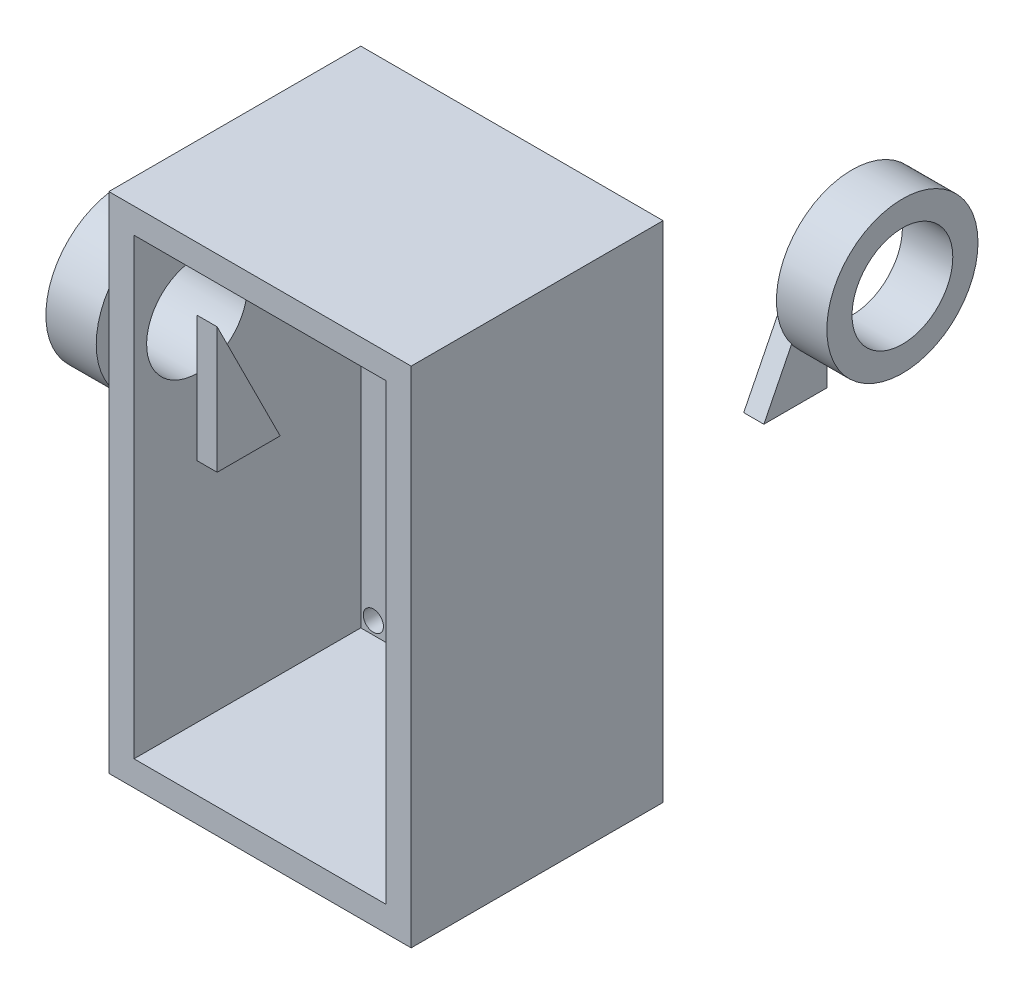
SolidWorks part; units mm, degrees
ref_plane "前视基准面" through (0, 0, 0) normal (0, 0, 1) x (1, 0, 0)
ref_plane "上视基准面" through (0, 0, 0) normal (0, 1, 0) x (1, 0, 0)
ref_plane "右视基准面" through (0, 0, 0) normal (1, 0, 0) x (0, 0, -1)
other "Configuration Table"
sketch "Sketch1" plane through (0, 0, 0) normal (0, 0, 1) x (1, 0, 0)
  line L1 (-60, -100) -> (60, -100)
  line L2 (-60, -100) -> (-60, 100)
  line L3 (-60, 100) -> (60, 100)
  line L4 (60, -100) -> (60, 100)
  line L5 (-60, -100) -> (60, 100) construction
  line L6 (-60, 100) -> (60, -100) construction
  point P0 (0, 0)
extrude "Boss-Extrude1" add sketch "Sketch1" along normal blind 100
ref_plane "Plane1" through (0, 0, 100) normal (0, 0, 1) x (1, 0, 0)
sketch "Sketch2" plane through (0, 0, 100) normal (0, 0, 1) x (1, 0, 0)
  line L1 (-50, -90) -> (50, -90)
  line L2 (-50, -90) -> (-50, 90)
  line L3 (-50, 90) -> (50, 90)
  line L4 (50, -90) -> (50, 90)
  line L5 (-50, -90) -> (50, 90) construction
  line L6 (-50, 90) -> (50, -90) construction
  point P0 (0, 0)
extrude "Cut-Extrude1" cut sketch "Sketch2" against normal blind 90
ref_plane "Plane2" through (-60, 0, 0) normal (1, 0, 0) x (0, 0, -1)
sketch "Sketch3" plane through (-60, 0, 0) normal (1, 0, 0) x (0, 0, -1)
  circle A0 centre (-75, 50) radius 30
extrude "Boss-Extrude2" add sketch "Sketch3" against normal blind 20
ref_plane "Plane3" through (60, 0, 0) normal (1, 0, 0) x (0, 0, -1)
sketch "Sketch4" plane through (60, 0, 0) normal (1, 0, 0) x (0, 0, -1)
  circle A0 centre (75, 50) radius 30
extrude "Boss-Extrude3" add sketch "Sketch4" along normal blind 20
ref_plane "Plane4" through (-80, 0, 0) normal (1, 0, 0) x (0, 0, -1)
sketch "Sketch5" plane through (-80, 0, 0) normal (1, 0, 0) x (0, 0, -1)
  circle A0 centre (-75, 50) radius 20
extrude "Cut-Extrude2" cut sketch "Sketch5" along normal blind 40
ref_plane "Plane5" through (80, 0, 0) normal (1, 0, 0) x (0, 0, -1)
sketch "Sketch6" plane through (80, 0, 0) normal (1, 0, 0) x (0, 0, -1)
  circle A0 centre (75, 50) radius 20
extrude "Cut-Extrude3" cut sketch "Sketch6" against normal blind 40
ref_plane "Plane6" through (-50, 0, 0) normal (1, 0, 0) x (0, 0, -1)
sketch "Sketch7" plane through (-50, 0, 0) normal (1, 0, 0) x (0, 0, -1)
  line L0 (-75, 50) -> (-75, 0)
  line L1 (-75, 0) -> (-50, 0)
  line L2 (-50, 0) -> (-75, 50)
extrude "Boss-Extrude4" add sketch "Sketch7" along normal blind 8
ref_plane "Plane7" through (50, 0, 0) normal (1, 0, 0) x (0, 0, -1)
sketch "Sketch8" plane through (50, 0, 0) normal (1, 0, 0) x (0, 0, -1)
  line L0 (75, 50) -> (75, 0)
  line L1 (75, 0) -> (50, 0)
  line L2 (50, 0) -> (75, 50)
extrude "Boss-Extrude5" add sketch "Sketch8" against normal blind 8
ref_plane "Plane8" through (0, 0, 0) normal (0, 0, 1) x (1, 0, 0)
sketch "Sketch9" plane through (0, 0, 0) normal (0, 0, 1) x (1, 0, 0)
  circle A0 centre (45, 85) radius 4
  circle A1 centre (-45, 85) radius 4
  circle A2 centre (45, -85) radius 4
  circle A3 centre (-45, -85) radius 4
extrude "Cut-Extrude4" cut sketch "Sketch9" along normal blind 10
ref_plane "Bottom_Base_Face" through (0, 0, 0) normal (0, 0, 1) x (1, 0, 0)
sketch3d "3DSketch1"
  line L0 (-60, 75, 50) -> (-100, 75, 50) construction
ref_axis "Bearing_Axis_Left" through (-60, 75, 50) along (-1, 0, 0)
sketch3d "3DSketch2"
  line L0 (60, -75, 50) -> (100, -75, 50) construction
ref_axis "Bearing_Axis_Right" through (60, -75, 50) along (1, 0, 0)
